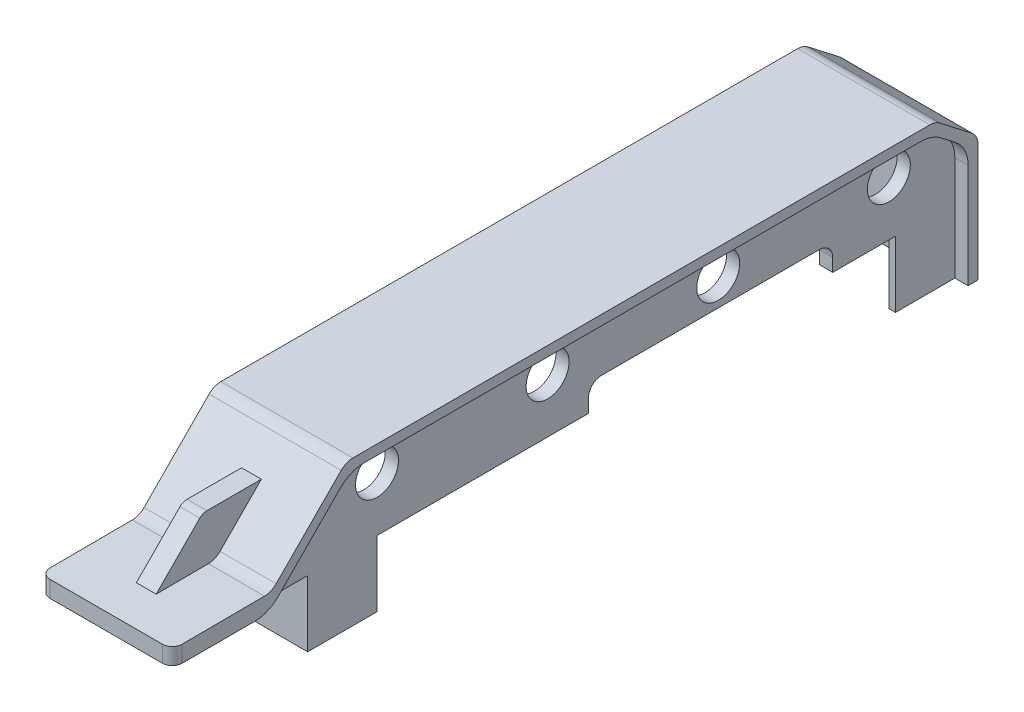
SolidWorks part; units mm, degrees
ref_plane "Front Plane" through (0, 0, 0) normal (0, 0, 1) x (1, 0, 0)
ref_plane "Top Plane" through (0, 0, 0) normal (0, 1, 0) x (1, 0, 0)
ref_plane "Right Plane" through (0, 0, 0) normal (1, 0, 0) x (0, 0, -1)
sketch "Sketch1" plane through (0, 0, 0) normal (1, 0, 0) x (0, 0, -1)
  line L0 (0, 0) -> (-130, 0)
  line L1 (0, 0) -> (74, 0) construction
  line L2 (0, 0) -> (0, 8)
  line L3 (0, 8) -> (74, 8)
  line L4 (74, 8) -> (74, 0)
  line L5 (74, 0) -> (114, 0)
  line L6 (-130, 0) -> (-130, 5)
  line L7 (-130, 5) -> (-100.0004, 5.1483)
  line L8 (-100.0004, 5.1483) -> (-77.3734, 28)
  line L9 (114, 0) -> (114, 18)
  line L10 (114, 18) -> (101.0882, 28)
  line L11 (101.0882, 28) -> (-77.3734, 28)
  dimension "D1" = 130
  dimension "D2" = 74
  dimension "D3" = 8
  dimension "D4" = 40
  dimension "D5" = 30
  dimension "D6" = 5
  dimension "D7" = 135
  dimension "D8" = 20
  dimension "D9" = 18
extrude "Boss-Extrude1" add sketch "Sketch1" along normal blind 40
sketch "Sketch4" plane through (40, 0, 0) normal (1, 0, 0) x (0, 0, -1)
  line L11 (-130, 0) -> (0, 0) construction
  line L12 (-130, 0) -> (0, 0) construction
  line L13 (-100.8762, 0) -> (0, 0)
  line L14 (0, 0) -> (111, 0)
  line L15 (74, 0) -> (114, 0) construction
  line L16 (111, 0) -> (111, 3)
  line L22 (-3, 3) -> (-3, 11)
  line L23 (-3, 11) -> (77, 11)
  line L24 (77, 11) -> (77, 3)
  line L25 (77, 3) -> (111, 3)
  line L26 (111, 3) -> (111, 16.5289)
  line L27 (111, 16.5289) -> (100.0623, 25)
  line L28 (100.0623, 25) -> (-76.1221, 25)
  line L29 (-76.1221, 25) -> (-97.9057, 3)
  line L30 (-97.9057, 3) -> (-3, 3)
  line L35 (111, 3) -> (111, 16.5289)
  line L36 (111, 16.5289) -> (100.0623, 25)
  line L37 (100.0623, 25) -> (-76.1221, 25)
  line L38 (-76.1221, 25) -> (-100.8762, 0)
  dimension "D1" = 3
extrude "Cut-Extrude1" cut sketch "Sketch4" against normal blind 4
ref_plane "Plane1" through (20, 0, 0) normal (1, 0, 0) x (0, 0, -1)
mirror "Mirror2" about plane through (20, 0, 0) normal (1, 0, 0) of "Cut-Extrude1"
fillet "Fillet1" radius 4 2 edges at (20, 8, -74) (20, 8, 0)
fillet "Fillet2" radius 10 8 edges at (38, 16.5289, -111) (38, 25, -100.0623) (2, 16.5289, -111) (2, 25, -100.0623) (2, 25, 76.1221) (38, 25, 76.1221) (2, 0, 100.8762) (38, 0, 100.8762)
fillet "Fillet3" radius 5 4 edges at (20, 18, -114) (20, 28, -101.0882) (20, 28, 77.3734) (20, 5.1483, 100.0004)
fillet "Fillet4" radius 3 2 edges at (0, 2.5, 130) (40, 2.5, 130)
sketch "Sketch5" plane through (20, 0, 0) normal (1, 0, 0) x (0, 0, -1)
  line L0 (-117.866, 5.06) -> (-103.7939, 19.2718)
  line L1 (-102.0714, 5.138) -> (-127, 5.0148) construction
  line L2 (-78.8408, 26.518) -> (-98.5432, 6.62) construction
  line L3 (-103.7939, 19.2718) -> (-72.6053, 19.2718)
  line L4 (-117.866, 5.06) -> (-95.866, 5.06)
  line L5 (-79.0569, 22.036) -> (-97.9414, 2.964) construction
  line L6 (-72.6053, 19.2718) -> (-95.866, 5.06)
  dimension "D1" = 22
  dimension "D2" = 20
extrude "Boss-Extrude2" add sketch "Sketch5" along normal blind 3 and the other way blind 3
fillet "Fillet5" radius 3 1 edges at (20, 19.2718, 103.7939)
sketch "Sketch6" plane through (0, 0, 0) normal (0, -1, 0) x (1, 0, 0)
  line L0 (40, -111) -> (40, -114) construction
  line L1 (0, -111) -> (0, -114) construction
  line L2 (0, -111) -> (4, -111)
  line L3 (0, -111) -> (0, -114)
  line L4 (0, -114) -> (40, -114)
  line L5 (40, -111) -> (40, -114)
  line L6 (0, -111) -> (40, -114) construction
  line L7 (0, -114) -> (40, -111) construction
  line L8 (4, -111) -> (0, -111) construction
  line L9 (40, -114) -> (0, -114) construction
  line L10 (4, -74) -> (4, -111) construction
  line L11 (4, -111) -> (36, -111) construction
  line L12 (4, -111) -> (4, -93)
  line L14 (36, -111) -> (36, -93)
  line L15 (6, -93) -> (6, -109)
  line L16 (6, -109) -> (34, -109)
  line L17 (36, -74) -> (36, -111) construction
  line L18 (4, -111) -> (36, -111) construction
  line L19 (36, -111) -> (40, -111)
  line L20 (4, -93) -> (6, -93)
  line L25 (34, -109) -> (34, -93)
  line L27 (36, -93) -> (34, -93)
  point P6 (20, -112.5)
  point P16 (20, -102)
  point P21 (20, -102)
  point P25 (34, -107.9926)
  dimension "D1" = 18
  dimension "D2" = 2
  dimension "D3" = 2
extrude "Boss-Extrude3" add sketch "Sketch6" along normal blind 20
sketch "Sketch7" plane through (0, -20, 0) normal (0, -1, 0) x (1, 0, 0)
  line L0 (34, -109) -> (34, -95) construction
  line L1 (34, -95) -> (6, -95)
  line L2 (34, -95) -> (34, -93)
  line L3 (34, -93) -> (6, -93)
  line L4 (6, -95) -> (6, -93)
  line L5 (34, -95) -> (6, -93) construction
  line L6 (34, -93) -> (6, -95) construction
  line L7 (34, -95) -> (6, -95) construction
  line L8 (36, -93) -> (4, -93) construction
  line L9 (6, -95) -> (6, -109) construction
  point P4 (20, -94)
sketch "Sketch8" plane through (0, 0, 0) normal (0, -1, 0) x (1, 0, 0)
  line L5 (36, 85) -> (36, 130) construction
  line L6 (36, 105.0473) -> (36, 0) construction
  line L8 (37, 130) -> (3, 130) construction
  line L9 (4, 105.0473) -> (4, 0) construction
  line L10 (36, 85) -> (4, 85)
  line L11 (36, 85) -> (36, 64)
  line L12 (36, 64) -> (34, 64)
  line L13 (4, 85) -> (4, 64)
  line L14 (36, 85) -> (4, 64) construction
  line L15 (36, 64) -> (4, 85) construction
  line L16 (34, 64) -> (6, 64) construction
  line L17 (6, 64) -> (34, 64) construction
  line L18 (6, 64) -> (6, 83)
  line L19 (6, 83) -> (34, 83)
  line L20 (34, 64) -> (34, 83)
  line L21 (6, 64) -> (34, 83) construction
  line L22 (6, 83) -> (34, 64) construction
  line L23 (6, 64) -> (4, 64)
  point P9 (20, 74.5)
  point P16 (20, 73.5)
  dimension "D1" = 45
  dimension "D2" = 21
  dimension "D3" = 2
  dimension "D4" = 2
  dimension "D5" = 2
extrude "Boss-Extrude4" add sketch "Sketch8" along normal blind 20
sketch "Sketch9" plane through (0, 0, 0) normal (0, -1, 0) x (1, 0, 0)
  line L0 (6, 64) -> (6, 83) construction
  line L1 (6, 64) -> (34, 64)
  line L2 (6, 64) -> (6, 66)
  line L3 (6, 66) -> (34, 66)
  line L4 (34, 64) -> (34, 66)
  line L5 (6, 64) -> (34, 66) construction
  line L6 (6, 66) -> (34, 64) construction
  line L7 (34, 83) -> (34, 64) construction
  point P4 (20, 65)
  dimension "D1" = 2
extrude "Boss-Extrude5" [suppressed] add sketch "Sketch9" along normal blind 8
extrude "Cut-Extrude2" [suppressed] cut sketch "Sketch7" against normal blind 5 contours L3 L4 L1 L2
sketch "Sketch12" plane through (0, 0, 85) normal (0, 0, 1) x (1, 0, 0)
  line L0 (30.75, -8.75) -> (36, -8.75) construction
  line L1 (30.75, -8.75) -> (30.75, -5) construction
  line L3 (12.5, -20) -> (12.5, -5) construction
  line L6 (0, -12.5) -> (25, -12.5) construction
  line L7 (4, -20) -> (36, -20) construction
  line L8 (4, -20) -> (4, 0) construction
  line L9 (36, -20) -> (36, 0) construction
  circle A0 centre (30.75, -16.25) radius 1.6
  circle A1 centre (-5.75, -16.25) radius 1.6
  circle A2 centre (-5.75, -8.75) radius 1.6
  circle A3 centre (30.75, -8.75) radius 1.6
  circle A4 centre (-5.75, -16.25) radius 3 construction
  dimension "D1" = 3.2
  dimension "D2" = 5.25
  dimension "D3" = 3.75
extrude "Cut-Extrude4" [suppressed] cut sketch "Sketch12" against normal up to surface (2 mm away) up to face at (20, -10, 83)
sketch "Sketch14" plane through (20, 0, 0) normal (1, 0, 0) x (0, 0, -1)
  line L0 (-83, 0) -> (-83, 13.4752)
  line L10 (109, 10.5924) -> (95.5924, 24)
  line L12 (109, 0) -> (-83, 0)
  line L15 (-72.4752, 24) -> (-83, 13.4752)
  line L18 (95.5924, 24) -> (-72.4752, 24)
  line L20 (99.3784, 28) -> (-75.2879, 28) construction
  line L22 (109, 0) -> (109, 10.5924)
  dimension "D4" = 135
  dimension "D6" = 4
extrude "Cut-Extrude5" cut sketch "Sketch14" against normal blind 12 and the other way blind 12
sketch "Sketch15" plane through (4, 0, 0) normal (-1, 0, 0) x (0, 0, 1)
  line L0 (-37, 8) -> (-37, 25) construction
  line L1 (-70, 8) -> (-4, 8) construction
  line L2 (-96.6427, 25) -> (71.951, 25) construction
  line L3 (-37, 16.5) -> (-111, 16.5) construction
  line L4 (-37, 16.5) -> (84, 16.5) construction
  line L6 (-111, 16.5) -> (-13.5, 16.5) construction
  line L7 (-13.5, 16.5) -> (-13.5, 8) construction
  line L8 (-111, 16.5) -> (-91, 16.5) construction
  circle A1 centre (-91, 16.5) radius 6.5
  circle A2 centre (-39.3333, 16.5) radius 6.5
  circle A3 centre (64, 16.5) radius 6.5
  circle A4 centre (12.3333, 16.5) radius 6.5
  dimension "D5" = 13
  dimension "D1" = 74
  dimension "D2" = 121
  dimension "D3" = 97.5
  dimension "D4" = 20
  dimension "D6" = 51.6667
extrude "Cut-Extrude6" cut sketch "Sketch15" against normal up to surface (32 mm away) up to face at (36, 3.6037, -13.6013)
sketch "Sketch11" plane through (0, 0, -114) normal (0, 0, -1) x (-1, 0, 0)
  line L0 (0, -20) -> (0, -12.5) construction
  line L1 (0, -20) -> (-40, -20) construction
  line L2 (0, -20) -> (0, 15.5482) construction
  line L3 (0, -16.25) -> (-40, -16.25) construction
  line L4 (-40, -20) -> (-40, 15.5482) construction
  line L5 (0, -16.25) -> (-9.25, -16.25) construction
  line L6 (-20, -20) -> (-20, -5) construction
  line L7 (0, -20) -> (0, -16.25)
  line L8 (-40, -20) -> (-40, -12.5) construction
  line L9 (-40, -12.5) -> (0, -12.5) construction
  circle A0 centre (-9.25, -16.25) radius 1.6
  circle A1 centre (-30.75, -16.25) radius 1.6
  circle A2 centre (-30.75, -8.75) radius 1.6
  circle A3 centre (-9.25, -8.75) radius 1.6
  circle A4 centre (-30.75, -16.25) radius 3 construction
  dimension "D2" = 3.2
  dimension "D5" = 6
  dimension "D1" = 9.25
  dimension "D3" = 3.75
  dimension "D4" = 7.5
extrude "Cut-Extrude3" [suppressed] cut sketch "Sketch11" against normal up to surface (19 mm away) contours A1 | A2 | A3 | A0
